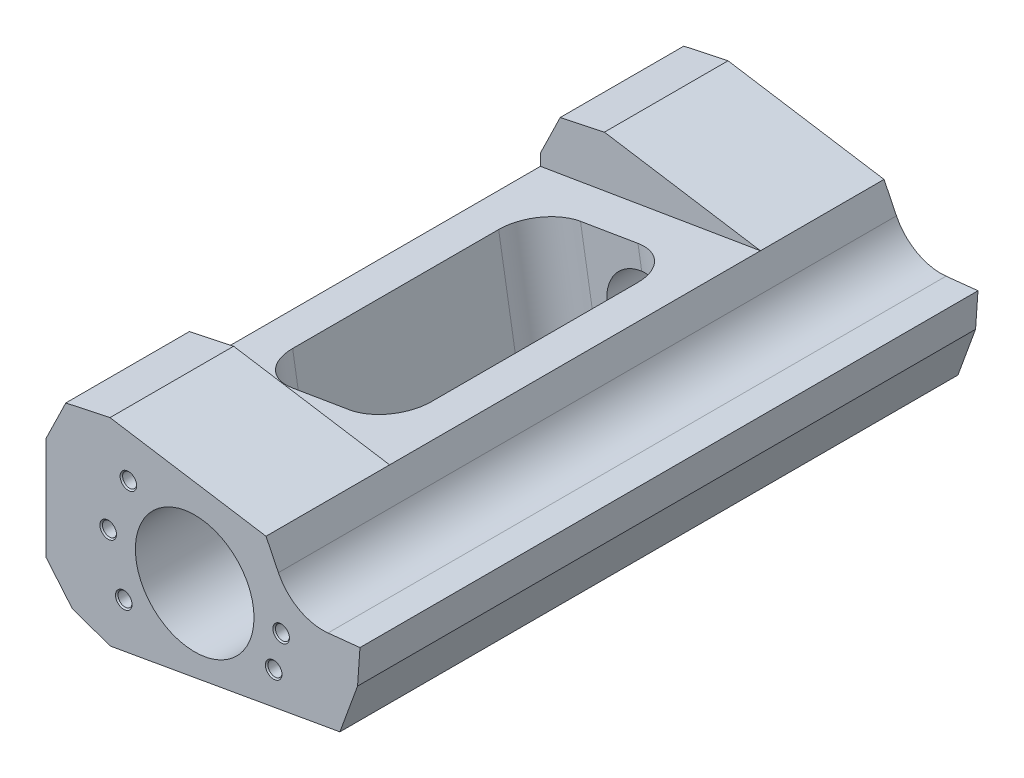
SolidWorks part; units mm, degrees
note: The reader was unsure of these and kept them because the rebuilt part matched: shared geometry of "Esboço7<3>", "Esboço7<4>".
material "AISI 4340 Aço, normalizado"
ref_plane "Plano frontal" through (0, 0, 0) normal (0, 0, 1) x (1, 0, 0)
ref_plane "Plano superior" through (0, 0, 0) normal (0, 1, 0) x (1, 0, 0)
ref_plane "Plano direito" through (0, 0, 0) normal (1, 0, 0) x (0, 0, -1)
other "Centro da massa"
sketch "Esboço1" plane through (0, 0, 0) normal (0, 0, 1) x (1, 0, 0)
  line L0 (0, 0) -> (23.1081, 0) construction
  line L1 (65, 0) -> (64.021, -14)
  line L2 (0, 0) -> (0, 38.7297) construction
  line L39 (27, 20) -> (-36.1134, 29.9962)
  line L40 (-36.1134, 29.9962) -> (-54, 26.1908)
  line L41 (-54, 26.1908) -> (-62, 9.7466)
  line L42 (-62, 9.7466) -> (-62, -31.874)
  line L43 (-62, -31.874) -> (-51.4851, -44.4051)
  line L44 (-51.4851, -44.4051) -> (-36.1134, -50)
  line L45 (-36.1134, -50) -> (56.8866, -33.6016)
  line L47 (56.8866, -33.6016) -> (64.021, -14)
  line L49 (65, 0) -> (52.0712, -1.3589)
  line L50 (32.0133, 9.7466) -> (27, 20)
  arc A0 (52.0712, -1.3589) -> (32.0133, 9.7466) centre (49.9806, 18.5316) cw
  dimension "D2" = 20
  dimension "D1" = 6
  dimension "D3" = 65
  dimension "D4" = 4
  dimension "D5" = 20
  dimension "D6" = 14
  dimension "D7" = 10
  dimension "D8" = 50
  dimension "D9" = 140
  dimension "D10" = 150
  dimension "D11" = 93
  dimension "D12" = 62
  dimension "D13" = 9
  dimension "D14" = 20
  dimension "D15" = 54
  dimension "D16" = 13
  dimension "D17" = 27
extrude "EXTRUSÃO PRINCIPAL" add sketch "Esboço1" along normal blind 250 contours L40 L41 L42 L43 L44 L45 L47 L1 L49 A0 L50 L39
scale "ESCALA" scale about centroid uniform scaling yes scale factor 1.5
sketch "Esboço4" plane through (0, 0, -62.5) normal (0, 0, -1) x (-1, 0, 0)
  line L1 (89.4104, 19.96) -> (89.4104, -42.4709) construction
  line L3 (89.4104, -42.4709) -> (73.6381, -61.2676) construction
  line L4 (73.6381, -61.2676) -> (50.5805, -69.6599) construction
  line L5 (50.5805, -69.6599) -> (-88.9195, -45.0623) construction
  line L7 (89.4104, 19.96) -> (89.4104, 12.96)
  line L8 (89.4104, -42.4709) -> (73.6381, -61.2676)
  line L9 (73.6381, -61.2676) -> (50.5805, -69.6599)
  line L10 (50.5805, -69.6599) -> (-88.9195, -45.0623)
  line L11 (50.5805, 50.3344) -> (-44.0896, 35.3401)
  line L12 (-44.0896, 35.3401) -> (-51.6096, 19.96)
  line L13 (-81.6964, 3.3018) -> (-101.0896, 5.3401)
  line L14 (-101.0896, 5.3401) -> (-99.6211, -15.6599)
  line L15 (-99.6211, -15.6599) -> (-88.9195, -45.0623)
  line L16 (-88.9195, -45.0623) -> (50.5805, -69.6599)
  line L17 (50.5805, -69.6599) -> (73.6381, -61.2676)
  line L18 (73.6381, -61.2676) -> (89.4104, -42.4709)
  line L19 (89.4104, -42.4709) -> (89.4104, 19.96)
  line L20 (89.4104, 19.96) -> (77.4104, 44.6263)
  line L21 (77.4104, 44.6263) -> (50.5805, 50.3344)
  line L22 (50.5805, 50.3344) -> (-44.0896, 35.3401)
  line L31 (89.4104, 19.96) -> (77.4104, 44.6263)
  line L32 (77.4104, 44.6263) -> (50.5805, 50.3344)
  line L37 (-44.0896, 35.3401) -> (89.4104, 12.96)
  line L39 (-51.6096, 19.96) -> (-44.0896, 35.3401) construction
  line L40 (-88.9195, -45.0623) -> (89.4104, -42.4709)
  arc A1 (-81.6964, 3.3018) -> (-51.6096, 19.96) centre (-78.5606, 33.1375) ccw
  dimension "D3" = 7
  dimension "D1" = 0
extrude "ALIVIO SUP./INF." cut sketch "Esboço4" against normal offset from surface (225 mm away) 75 from offset 75 offset against normal yes
sketch "Esboço6" plane through (-4.5573, 27.1849, 0) normal (-0.1653, 0.9862, 0) x (0.9862, 0.1653, 0)
  line L0 (-41.5624, -12.5) -> (49.3257, -12.5) construction
  line L1 (-36.0372, -37.5) -> (-0.6743, -37.5)
  line L2 (-61.0372, -62.5) -> (-61.0372, -187.5)
  line L3 (-36.0372, -212.5) -> (-0.6743, -212.5)
  line L4 (24.3257, -62.5) -> (24.3257, -187.5)
  line L5 (49.3257, -237.5) -> (-41.5624, -237.5) construction
  line L6 (-86.0372, -237.5) -> (-86.0372, -12.5) construction
  line L7 (49.3257, -237.5) -> (49.3257, -12.5) construction
  arc A0 (-0.6743, -212.5) -> (24.3257, -187.5) centre (-0.6743, -187.5) ccw
  arc A1 (-61.0372, -187.5) -> (-36.0372, -212.5) centre (-36.0372, -187.5) ccw
  arc A2 (-0.6743, -37.5) -> (24.3257, -62.5) centre (-0.6743, -62.5) cw
  arc A3 (-36.0372, -37.5) -> (-61.0372, -62.5) centre (-36.0372, -62.5) ccw
  dimension "D5" = 25
  dimension "D1" = 25
  dimension "D2" = 25
  dimension "D3" = 25
  dimension "D4" = 25
extrude "ALÍVIO CENTRAL" cut sketch "Esboço6" against normal through all and the other way through all
hole_wizard "FUROS DIR." positions "Esboço11" profile "Esboço12" tap size "M10" standard "ISO"
sketch "Esboço11" plane through (0, 0, 312.5) normal (0, 0, 1) x (1, 0, 0)
  line L0 (0.7803, -11.103) -> (-39.4371, 22.6433) construction
  line L1 (0.7803, -11.103) -> (-42.2252, -41.2158) construction
  line L2 (0.7803, -11.103) -> (48.7414, -32.4567) construction
  line L4 (0.7803, -11.103) -> (-51.7197, -11.103) construction
  line L5 (0.7803, -11.103) -> (53.2803, -11.103) construction
  circle A0 centre (0.7803, -11.103) radius 52.5
  point P5 (-39.4371, 22.6433)
  point P7 (-51.6816, -9.103)
  point P9 (-42.2252, -41.2158)
  point P11 (48.7414, -32.4567)
  point P13 (53.2803, -11.103)
  dimension "D1" = 105
  dimension "D2" = 40
  dimension "D3" = 35
  dimension "D4" = 24
  dimension "D5" = 4
sketch "Esboço12" plane through (53.2803, -11.103, 312.5) normal (1, 0, 0) x (0, -1, 0)
  line L0 (0, 0) -> (0, 30.0537)
  line L1 (0, 30.0537) -> (4.25, 27.5)
  line L2 (4.25, 27.5) -> (4.25, 0.775)
  line L3 (4.25, 0.775) -> (5.025, 0)
  line L5 (5.025, 0) -> (0, 0)
  line L6 (-4.25, 0.775) -> (-5.025, 0) construction
  line L10 (0, 30.0537) -> (-4.25, 27.5) construction
  line L11 (0, -6.35) -> (0, 107.95) construction
  dimension "Tap Drill Dia." = 8.5
  dimension "Tap Drill Depth" = 27.5
  dimension "Near C'Sink Dia." = 10.05
  dimension "Near C'Sink Angle" = 90
  dimension "Drill Angle" = 118
cosmetic thread "Rosca de furo6" parameters "D1"=20, "D2"=10
cosmetic thread "Rosca de furo7" parameters "D1"=20, "D2"=10
cosmetic thread "Rosca de furo8" parameters "D1"=20, "D2"=10
cosmetic thread "Rosca de furo9" parameters "D1"=20, "D2"=10
cosmetic thread "Rosca de furo10" parameters "D1"=20, "D2"=10
hole_wizard "FUROS ESQ." positions "Esboço13" profile "Esboço14" tap size "M10" standard "ISO"
sketch "Esboço13" plane through (0, 0, -62.5) normal (0, 0, -1) x (-1, 0, 0)
  circle A0 centre (-0.7803, -11.103) radius 52.5 construction
  point P0 (39.4371, 22.6433)
  point P3 (51.6816, -9.103)
  point P6 (42.2252, -41.2158)
  point P9 (-48.7414, -32.4567)
  point P13 (-53.2803, -11.103)
sketch "Esboço14" plane through (-39.4371, 22.6433, -62.5) normal (1, 0, 0) x (0, 1, 0)
  line L0 (0, 0) -> (0, 30.0537)
  line L1 (0, 30.0537) -> (4.25, 27.5)
  line L2 (4.25, 27.5) -> (4.25, 0.775)
  line L3 (4.25, 0.775) -> (5.025, 0)
  line L5 (5.025, 0) -> (0, 0)
  line L6 (-4.25, 0.775) -> (-5.025, 0) construction
  line L10 (0, 30.0537) -> (-4.25, 27.5) construction
  line L11 (0, -6.35) -> (0, 107.95) construction
  dimension "Tap Drill Dia." = 8.5
  dimension "Tap Drill Depth" = 27.5
  dimension "Near C'Sink Dia." = 10.05
  dimension "Near C'Sink Angle" = 90
  dimension "Drill Angle" = 118
cosmetic thread "Rosca de furo11" parameters "D1"=20, "D2"=10
cosmetic thread "Rosca de furo12" parameters "D1"=20, "D2"=10
cosmetic thread "Rosca de furo13" parameters "D1"=20, "D2"=10
cosmetic thread "Rosca de furo14" parameters "D1"=20, "D2"=10
cosmetic thread "Rosca de furo15" parameters "D1"=20, "D2"=10
sketch "Esboço7" plane through (0, 0, 312.5) normal (0, 0, 1) x (1, 0, 0)
  line L0 (104.775, -11.0983) -> (-104.775, -11.0983) construction
  line L1 (0.8091, 55) -> (0.8091, -55) construction
  circle A0 centre (0.8091, -11.0983) radius 36
  circle A1 centre (0.8091, -11.0983) radius 25
  point P2 (0, 0)
  point P3 (11.6914, -8.0963)
  point P4 (0, 0)
  point P5 (0, 0)
  point P6 (0, 0)
  point P7 (18.8104, -35.5422)
  point P8 (0, 0)
  point P9 (0, 0)
  point P10 (0.8091, -11.0983)
  point P13 (0, 0)
  point P14 (0, 0)
  dimension "D1" = 72
  dimension "D2" = 50
other "Ponto de referência do centro da massa1"
ref_plane "Plano1" through (0.8091, 0, 0) normal (-1, 0, 0) x (0, 0, 1)
ref_plane "Plano2" through (0, -11.0983, 0) normal (0, 1, 0) x (1, 0, 0)
extrude "FURO EIXO" cut sketch "Esboço7<3>" against normal through all contours A1
sketch "Esboço7<3>" plane through (0, 0, 312.5) normal (0, 0, 1) x (1, 0, 0) same geometry as "Esboço7"
extrude "REBAIXO ROLAMENTO ESQ." cut sketch "Esboço7" against normal blind 69 contours A0
extrude "REBAIXO ROLAMENTO DIR." cut sketch "Esboço7<4>" along normal blind 69 from surface at -375 starting at face at (25.8091, -11.0983, -62.5)
sketch "Esboço7<4>" plane through (0, 0, 312.5) normal (0, 0, 1) x (1, 0, 0) same geometry as "Esboço7"
sketch "CONTORNO " plane through (0, 0, 312.5) normal (0, 0, 1) x (1, 0, 0)
  line L22 (44.0896, 35.3401) -> (-50.5805, 50.3344)
  line L23 (-50.5805, 50.3344) -> (-77.4104, 44.6263)
  line L24 (-77.4104, 44.6263) -> (-89.4104, 19.96)
  line L25 (-89.4104, 19.96) -> (-89.4104, -42.4709)
  line L26 (-89.4104, -42.4709) -> (-73.6381, -61.2676)
  line L27 (-73.6381, -61.2676) -> (-50.5805, -69.6599)
  line L28 (-50.5805, -69.6599) -> (88.9195, -45.0623)
  line L29 (88.9195, -45.0623) -> (99.6211, -15.6599)
  line L30 (99.6211, -15.6599) -> (101.0896, 5.3401)
  line L31 (101.0896, 5.3401) -> (81.6964, 3.3018)
  line L32 (51.6096, 19.96) -> (44.0896, 35.3401)
  line L33 (44.0896, 35.3401) -> (-50.5805, 50.3344)
  line L34 (-50.5805, 50.3344) -> (-77.4104, 44.6263)
  line L35 (-77.4104, 44.6263) -> (-89.4104, 19.96)
  line L36 (-89.4104, 19.96) -> (-89.4104, -42.4709)
  line L37 (-89.4104, -42.4709) -> (-73.6381, -61.2676)
  line L38 (-73.6381, -61.2676) -> (-50.5805, -69.6599)
  line L39 (-50.5805, -69.6599) -> (88.9195, -45.0623)
  line L40 (88.9195, -45.0623) -> (99.6211, -15.6599)
  line L41 (99.6211, -15.6599) -> (101.0896, 5.3401)
  line L42 (101.0896, 5.3401) -> (81.6964, 3.3018)
  line L43 (51.6096, 19.96) -> (44.0896, 35.3401)
  circle A1 centre (0.8091, -11.0983) radius 36 construction
  arc A2 (51.6096, 19.96) -> (81.6964, 3.3018) centre (78.5606, 33.1375) ccw
  arc A3 (51.6096, 19.96) -> (81.6964, 3.3018) centre (78.5606, 33.1375) ccw
  circle A4 centre (0.8091, -11.0983) radius 36
  dimension "D1" = 0
sketch "RAIO" plane through (0, 0, 312.5) normal (0, 0, 1) x (1, 0, 0)
  circle A0 centre (0.8091, -11.0983) radius 101.6189
  circle A1 centre (0.8091, -11.0983) radius 36 construction
